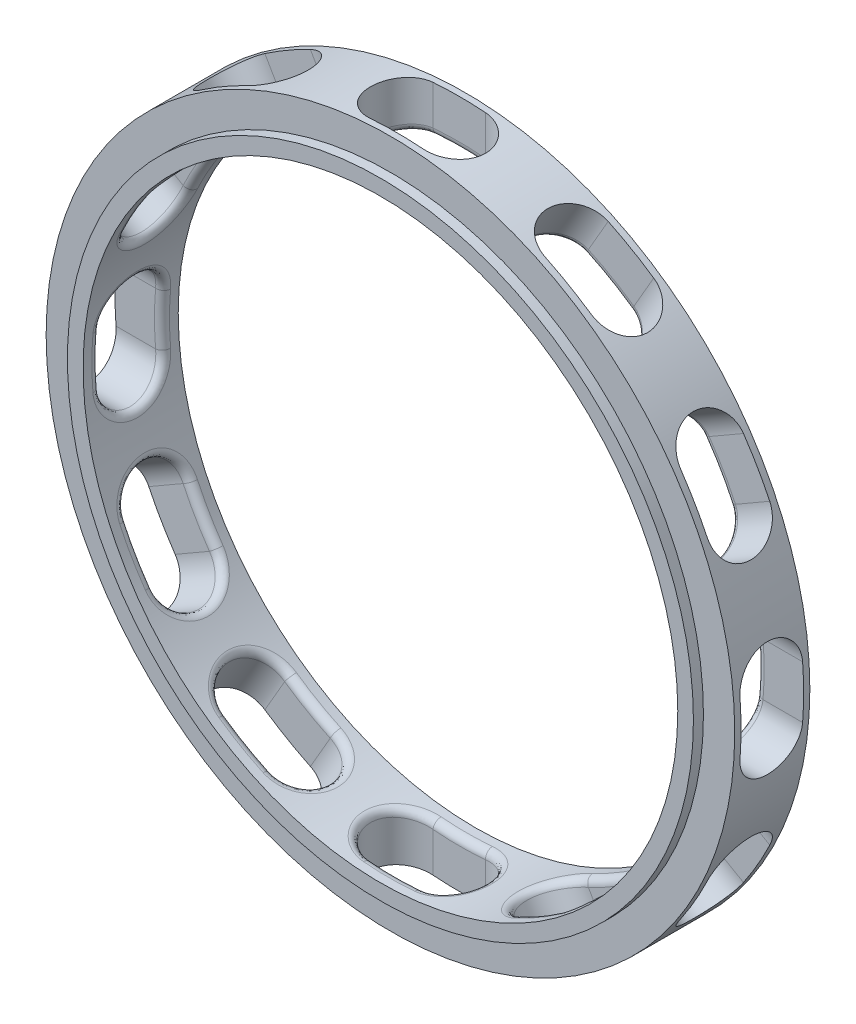
SolidWorks part; units mm, degrees
note: '?' marks a value the reader was unsure of.
ref_plane "Primary" through (0, 0, 0) normal (0, 0, 1) x (1, 0, 0)
ref_plane "Top" through (0, 0, 0) normal (0, 1, 0) x (1, 0, 0)
ref_plane "Side" through (0, 0, 0) normal (1, 0, 0) x (0, 0, -1)
sketch "Sketch1" plane through (0, 0, 0) normal (0, 0, 1) x (1, 0, 0)
  circle A0 centre (0, 0) radius 34.925
  circle A1 centre (0, 0) radius 30.1625
  circle A2 centre (0, 0) radius 31.75 construction
  dimension "D1" = 3.175
  dimension "D2" = 1.5875
  dimension "D3" = 63.5
  dimension "D4" = 60.325
  dimension "D5" = 69.85
extrude "Base-Extrude" add sketch "Sketch1" against normal mid plane 7.62
sketch "Sketch2" plane through (0, 0, 3.81) normal (0, 0, 1) x (1, 0, 0)
  circle A0 centre (0, 0) radius 30.1625 construction
  circle A1 centre (0, 0) radius 30.1625
  circle A2 centre (0, 0) radius 31.75
  circle A3 centre (0, 0) radius 31.75 construction
extrude "Boss-Extrude1" add sketch "Sketch2" along normal blind 1.016
sketch "Sketch3" plane through (-15.9725, 20.746, -3.81) normal (0, 0, -1) x (-1, 0, 0)
  circle A0 centre (-15.9725, -20.746) radius 31.75 construction
  circle A1 centre (-15.9725, -20.746) radius 30.1625
  circle A2 centre (-15.9725, -20.746) radius 31.75
  circle A5 centre (-15.9725, -20.746) radius 30.1625 construction
extrude "Boss-Extrude2" add sketch "Sketch3" along normal blind 1.016
ref_plane "Plane1" through (0, 38.1, 0) normal (0, 1, 0) x (-1, 0, 0)
sketch "Sketch4" plane through (0, 38.1, 0) normal (0, 1, 0) x (-1, 0, 0)
  line L0 (0, 11.2954) -> (0, -21.9089) construction
  line L1 (5.842, 0) -> (-5.842, 0) construction
  line L2 (2.667, -3.175) -> (-2.667, -3.175)
  line L4 (2.667, 3.175) -> (-2.667, 3.175)
  arc A0 (-2.667, 3.175) -> (-2.667, -3.175) centre (-2.667, 0) ccw
  arc A1 (2.667, -3.175) -> (2.667, 3.175) centre (2.667, 0) ccw
  dimension "D1" = 6.35
  dimension "D2" = 11.684
extrude "Cut-Extrude1" cut sketch "Sketch4" against normal blind 12.7
ref_axis "Axis1" through (0, 0, -53.81) along (0, 0, 1)?
pattern_circular "CirPattern5" count 12 every 30 about axis through (0, 0, -53.81) along (0, 0, 1)
fillet "Fillet1" radius 0.762
